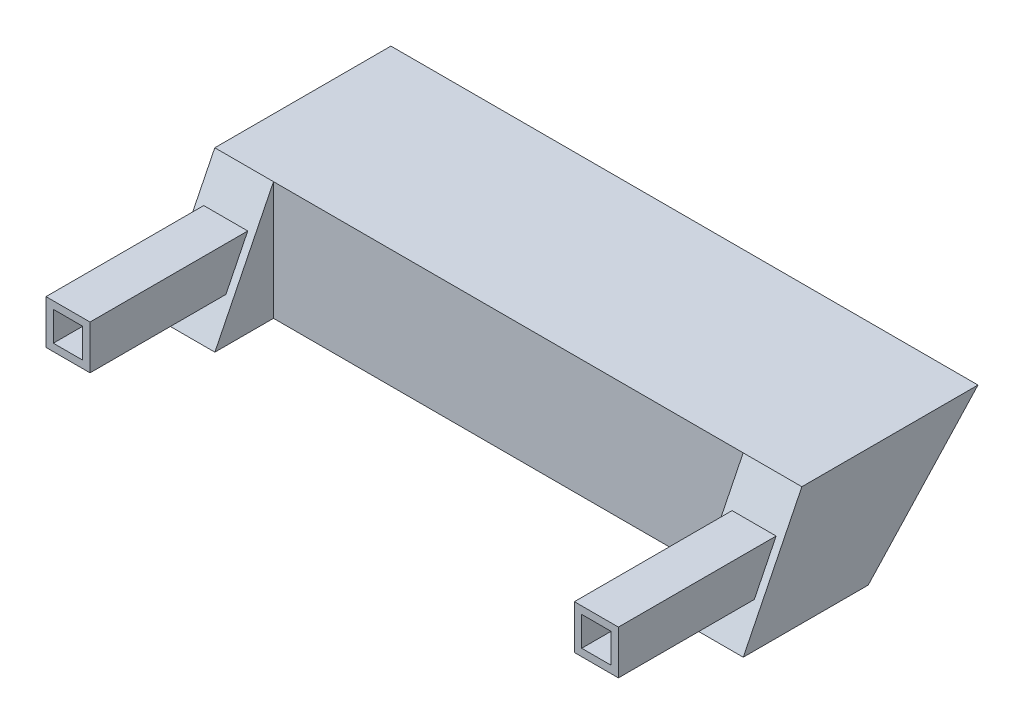
SolidWorks part; units mm, degrees
ref_plane "Front Plane" through (0, 0, 0) normal (0, 0, 1) x (1, 0, 0)
ref_plane "Top Plane" through (0, 0, 0) normal (0, 1, 0) x (1, 0, 0)
ref_plane "Right Plane" through (0, 0, 0) normal (1, 0, 0) x (0, 0, -1)
sketch "Sketch1" plane through (0, 0, 0) normal (1, 0, 0) x (0, 0, -1)
  line L0 (0, 0) -> (0, 51.2149)
  line L1 (0, 51.2149) -> (76.2, 51.2149)
  line L2 (76.2, 51.2149) -> (28.702, 0)
  line L3 (28.702, 0) -> (0, 0)
  dimension "D1" = 28.702
  dimension "D2" = 69.85
  dimension "D3" = 76.2
extrude "Boss-Extrude1" add sketch "Sketch1" along normal mid plane 254
sketch "Sketch3" plane through (0, 0, 0) normal (1, 0, 0) x (0, 0, -1)
  line L0 (0, 51.2149) -> (-25.3606, 0)
  line L1 (0, 55) -> (0, -55) construction
  line L2 (76.2, 51.2149) -> (0, 51.2149) construction
  line L3 (55, 0) -> (-55, 0) construction
  line L4 (-25.3606, 0) -> (0, 0)
  line L5 (0, 51.2149) -> (0, 0)
  dimension "D1" = 57.15
extrude "Boss-Extrude2" add sketch "Sketch3" along normal blind 25.4 from offset 101.6
mirror "Mirror1" about plane through (0, 0, 0) normal (1, 0, 0) of "Boss-Extrude2"
sketch "Sketch4" plane through (0, 0, 0) normal (0, 0, 1) x (1, 0, 0)
  line L0 (101.6, 51.2149) -> (127, 51.2149) construction
  line L1 (104.775, 35.1324) -> (123.825, 35.1324)
  line L2 (104.775, 35.1324) -> (104.775, 16.0824)
  line L3 (104.775, 16.0824) -> (123.825, 16.0824)
  line L4 (123.825, 35.1324) -> (123.825, 16.0824)
  line L5 (107.95, 31.9574) -> (120.65, 31.9574)
  line L6 (107.95, 31.9574) -> (107.95, 19.2574)
  line L7 (107.95, 19.2574) -> (120.65, 19.2574)
  line L8 (120.65, 31.9574) -> (120.65, 19.2574)
  line L9 (101.6, 51.2149) -> (101.6, 0) construction
  point P8 (114.3, 19.2574)
  point P9 (114.3, 16.0824)
  point P10 (120.65, 25.6074)
  point P11 (123.825, 25.6074)
  point P12 (114.3, 51.2149)
  point P17 (114.3, 35.1324)
  point P18 (101.6, 25.6074)
  point P21 (107.95, 25.6074)
  dimension "D1" = 19.05
  dimension "D2" = 12.7
extrude "Boss-Extrude3" add sketch "Sketch4" along normal blind 76.2
mirror "Mirror2" about plane through (0, 0, 0) normal (1, 0, 0) of "Boss-Extrude3"
equation "\"height\"= 2in"
equation "\"top length\"= 3in"
equation "\"bottom length\"= 1.13in"
equation "\"diag face\"= 2.75in"
equation "\"interface diag\"= 2.25in"
equation "\"D1@Sketch1\"=\"bottom length\""
equation "\"D2@Sketch1\"=\"diag face\""
equation "\"D3@Sketch1\"=\"top length\""
equation "\"width\"= 10in"
equation "\"D1@Boss-Extrude1\"=\"width\""
equation "\"D1@Sketch3\"=\"interface diag\""
equation "\"interfacewidth\"= 1in"
equation "\"D19@Boss-Extrude2\"=\"width\"/2  - \"interfacewidth\""
equation "\"D1@Boss-Extrude2\"=\"interfacewidth\""
equation "\"Connector OD\"= .75in"
equation "\"Connector ID\"= .5in"
equation "\"D1@Sketch4\"=\"Connector OD\""
equation "\"D2@Sketch4\"=\"Connector ID\""
equation "\"Connector Length\"= 3in"
equation "\"D1@Boss-Extrude3\"=\"Connector Length\""
